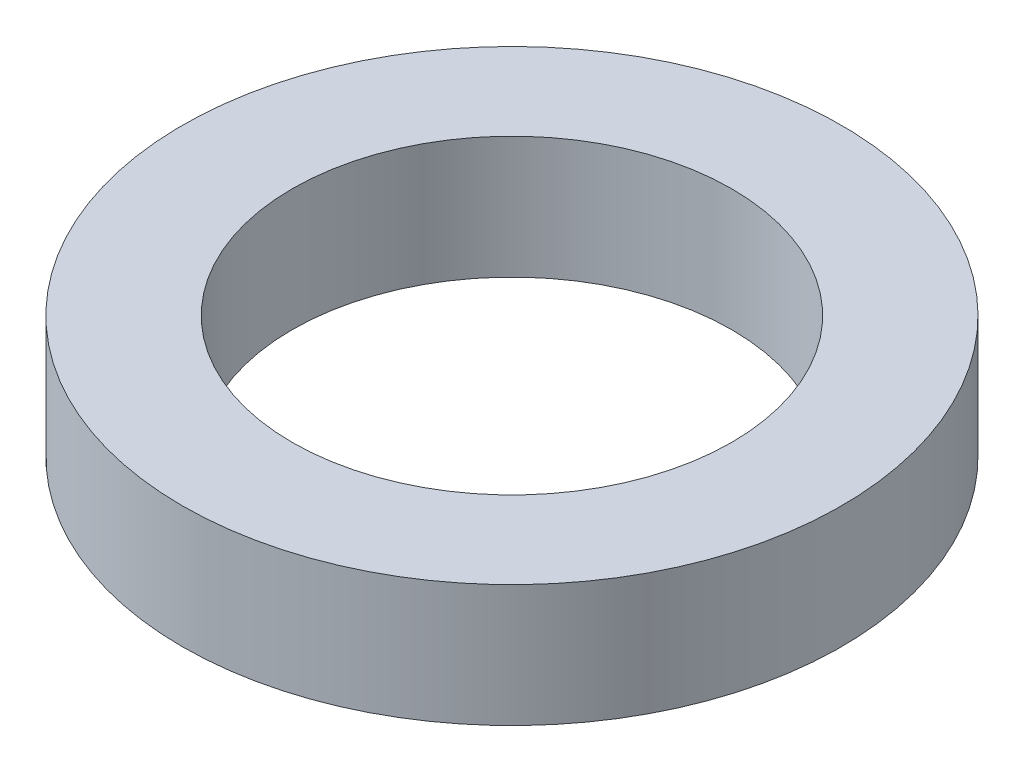
SolidWorks part; units mm, degrees
ref_plane "Front Plane" through (0, 0, 0) normal (0, 0, 1) x (1, 0, 0)
ref_plane "Top Plane" through (0, 0, 0) normal (0, 1, 0) x (1, 0, 0)
ref_plane "Right Plane" through (0, 0, 0) normal (1, 0, 0) x (0, 0, -1)
sketch "Sketch1" plane through (0, 0, 0) normal (0, 1, 0) x (1, 0, 0)
  circle A0 centre (0, 0) radius 67.5
  dimension "FLANGE_OD" = 135
extrude "Boss-Extrude1" add sketch "Sketch1" along normal blind 25
sketch "Sketch2" plane through (0, 0, 0) normal (0, 1, 0) x (1, 0, 0)
  circle A0 centre (0, 0) radius 45
  dimension "BORE_D" = 90
extrude "Cut-Extrude1" cut sketch "Sketch2" along normal through all
sketch "Sketch3" plane through (0, 25, 0) normal (0, 1, 0) x (1, 0, 0)
  circle A0 centre (0, 0) radius 26.9407 construction
  circle A1 centre (-26.9407, 0) radius 1.7048
  dimension "BOLT_D" = 3.4095
  dimension "BOLT_PCD" = 53.8813
extrude "Cut-Extrude2" cut sketch "Sketch3" against normal blind 17.3802 rebuild error yes
pattern_circular "CirPattern1" count 4 over 360 rebuild error yes
